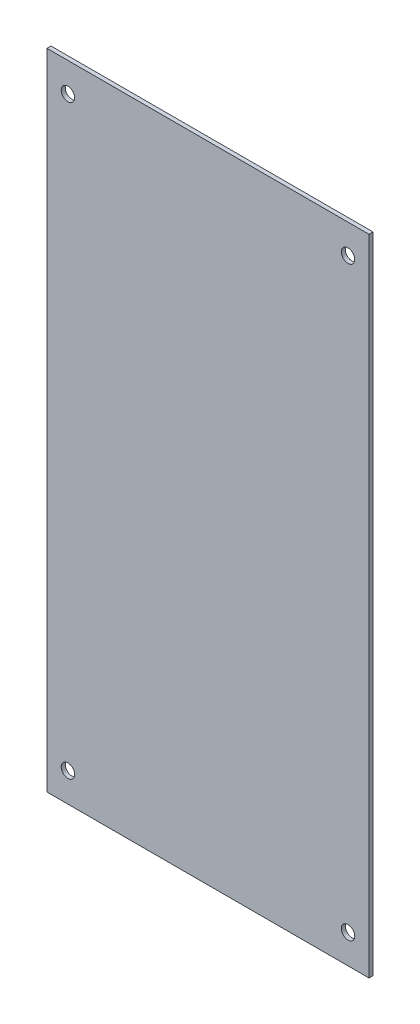
SolidWorks part; units mm, degrees
material "PVC Rigid"
ref_plane "Front Plane" through (0, 0, 0) normal (0, 0, 1) x (1, 0, 0)
ref_plane "Top Plane" through (0, 0, 0) normal (0, 1, 0) x (1, 0, 0)
ref_plane "Right Plane" through (0, 0, 0) normal (1, 0, 0) x (0, 0, -1)
sketch "Sketch1" plane through (0, 0, 0) normal (0, 0, 1) x (1, 0, 0)
  line L0 (-429.8803, -600.0743) -> (-275.2136, -600.0743) construction
  line L1 (-540.0164, 502.6455) -> (69.5836, 502.6455)
  line L2 (-540.0164, 502.6455) -> (-540.0164, -716.5545)
  line L3 (-540.0164, -716.5545) -> (69.5836, -716.5545)
  line L4 (69.5836, 502.6455) -> (69.5836, -716.5545)
  line L5 (-475.9005, 277.3141) -> (-189.9005, 277.3141) construction
  line L6 (58.8333, 238) -> (294.1667, 238) construction
  dimension "D1" = 609.6
  dimension "D2" = 1219.2
extrude "Boss-Extrude2" add sketch "Sketch1" along normal blind 7.62
sketch "Sketch2" plane through (0, 0, 7.62) normal (0, 0, 1) x (1, 0, 0)
  line L0 (-235.2164, 502.6455) -> (-235.2164, -716.5545) construction
  line L1 (69.5836, 502.6455) -> (-540.0164, 502.6455) construction
  line L2 (-540.0164, -716.5545) -> (69.5836, -716.5545) construction
  line L3 (-540.0164, -106.9545) -> (69.5836, -106.9545) construction
  line L4 (-540.0164, 502.6455) -> (-540.0164, -716.5545) construction
  line L5 (69.5836, -716.5545) -> (69.5836, 502.6455) construction
  circle A0 centre (-500.3266, 447.7179) radius 12.7
  circle A1 centre (29.8939, 447.7179) radius 12.7
  circle A2 centre (-500.3266, -661.6269) radius 12.7
  circle A3 centre (29.8939, -661.6269) radius 12.7
  dimension "D1" = 25.4
extrude "Cut-Extrude1" cut sketch "Sketch2" against normal through all
sketch "Sketch3" plane through (0, 0, 7.62) normal (0, 0, 1) x (1, 0, 0)
  line L0 (-460.9858, 207.9273) -> (-174.9858, 207.9273) construction
sketch "Sketch5" plane through (0, 0, 0) normal (0, 0, -1) x (-1, 0, 0)
  line L0 (217.6146, 0.4125) -> (503.6146, 0.4125) construction
